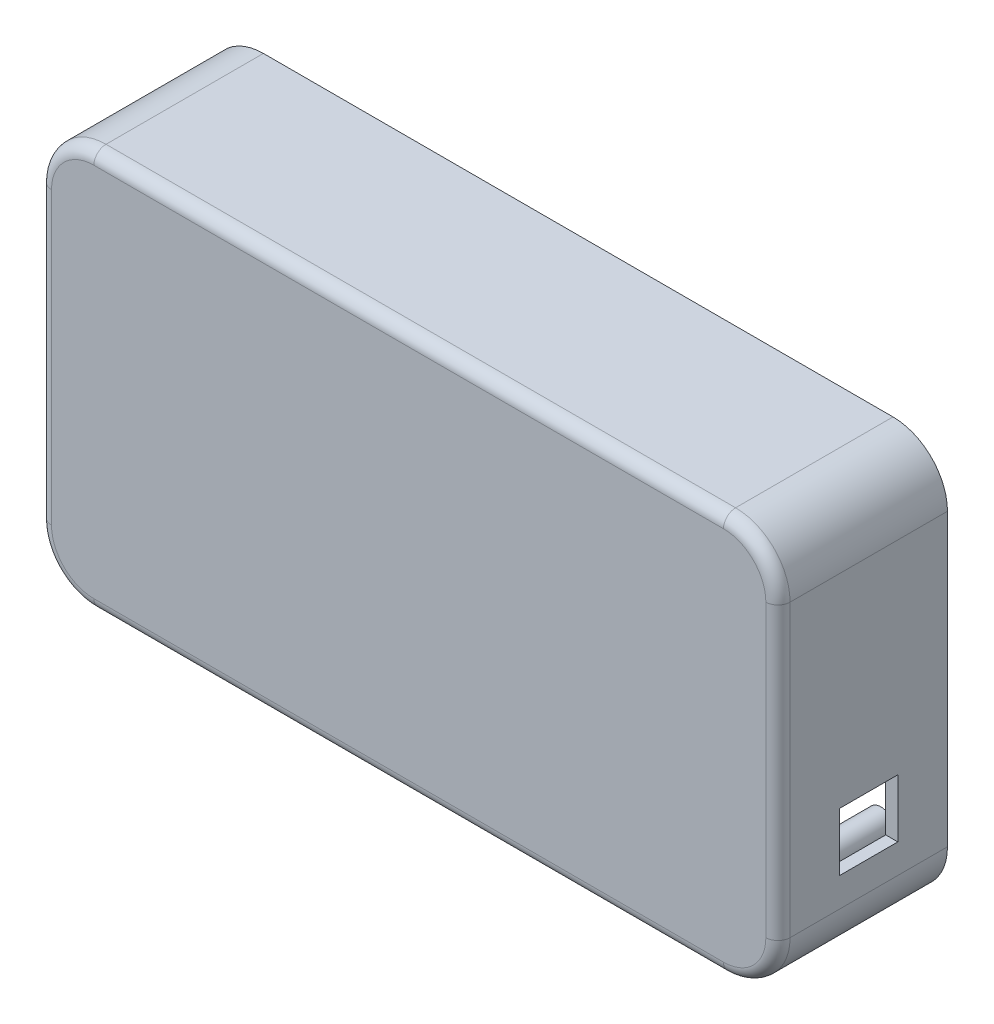
SolidWorks part; units mm, degrees
material "交联聚乙烯"
ref_plane "前视基准面" through (0, 0, 0) normal (0, 0, 1) x (1, 0, 0)
ref_plane "上视基准面" through (0, 0, 0) normal (0, 1, 0) x (1, 0, 0)
ref_plane "右视基准面" through (0, 0, 0) normal (1, 0, 0) x (0, 0, -1)
sketch "草图1" plane through (0, 0, 0) normal (0, 0, 1) x (1, 0, 0)
  line L1 (-130, 82.5) -> (130, 82.5)
  line L2 (-152.5, 60) -> (-152.5, -60)
  line L3 (-130, -82.5) -> (130, -82.5)
  line L4 (152.5, 60) -> (152.5, -60)
  line L5 (0, -82.5) -> (0, 82.5) construction
  line L6 (-152.5, 0) -> (152.5, 0) construction
  line L14 (-130, 77.5) -> (130, 77.5)
  line L15 (147.5, 60) -> (147.5, -60)
  line L16 (-130, -77.5) -> (130, -77.5)
  line L17 (-147.5, 60) -> (-147.5, -60)
  line L18 (-150.2, 60) -> (-150.2, -60)
  line L19 (-130, -80.2) -> (130, -80.2)
  line L20 (150.2, 60) -> (150.2, -60)
  line L21 (-130, 80.2) -> (130, 80.2)
  arc A0 (-130, -82.5) -> (-152.5, -60) centre (-130, -60) cw
  arc A1 (130, -82.5) -> (152.5, -60) centre (130, -60) ccw
  arc A2 (152.5, 60) -> (130, 82.5) centre (130, 60) ccw
  arc A3 (-152.5, 60) -> (-130, 82.5) centre (-130, 60) cw
  arc A12 (147.5, 60) -> (130, 77.5) centre (130, 60) ccw
  arc A13 (130, -77.5) -> (147.5, -60) centre (130, -60) ccw
  arc A14 (-130, -77.5) -> (-147.5, -60) centre (-130, -60) cw
  arc A15 (-147.5, 60) -> (-130, 77.5) centre (-130, 60) cw
  circle A16 centre (130, 60) radius 2.55
  circle A17 centre (130, 60) radius 5.55
  circle A18 centre (130, -60) radius 2.55
  circle A19 centre (130, -60) radius 5.55
  circle A20 centre (-130, 60) radius 2.55
  circle A21 centre (-130, 60) radius 5.55
  circle A22 centre (-130, -60) radius 2.55
  circle A23 centre (-130, -60) radius 5.55
  arc A24 (-130, -80.2) -> (-150.2, -60) centre (-130, -60) cw
  arc A25 (130, -80.2) -> (150.2, -60) centre (130, -60) ccw
  arc A26 (150.2, 60) -> (130, 80.2) centre (130, 60) ccw
  arc A27 (-150.2, 60) -> (-130, 80.2) centre (-130, 60) cw
  point P0 (0, 0)
  point P6 (-152.5, -82.5)
  point P9 (152.5, -82.5)
  point P12 (152.5, 82.5)
  point P49 (0, 0)
  dimension "D3" = 22.5
  dimension "D6" = 5.1
  dimension "D8" = 5.1
  dimension "D10" = 5.1
  dimension "D12" = 5.1
  dimension "D1" = 305
  dimension "D2" = 165
  dimension "D4" = 2.3
  dimension "D7" = 3
  dimension "D9" = 3
  dimension "D11" = 3
  dimension "D13" = 3
extrude "凸台-拉伸1" add sketch "草图1" along normal blind 70 contours A3 L1 A2 L4 A1 L3 A0 L2
extrude "切除-拉伸1" cut sketch "草图1<4>" along normal blind 65 contours A15 L17 A14 L16 A13 L15 A12 L14 region at (0, 0, 0)
sketch "草图1<4>" plane through (0, 0, 0) normal (0, 0, 1) x (1, 0, 0) same geometry as "草图1"
sketch "草图3" plane through (0, 0, 0) normal (0, 0, -1) x (-1, 0, 0)
extrude "切除-拉伸2" cut sketch "草图1<5>" along normal blind 5 contours A27 L21 A26 L20 A25 L19 A24 L18 L17 A15 L14 A12 L15 A13 L16 A14 region at (-144.0428, 74.0428, 0)
sketch "草图1<5>" plane through (0, 0, 0) normal (0, 0, 1) x (1, 0, 0) same geometry as "草图1"
extrude "切除-拉伸3" cut sketch "草图1<6>" along normal blind 5 contours A17 A16 region at (124.607, 60, 0)
sketch "草图1<6>" plane through (0, 0, 0) normal (0, 0, 1) x (1, 0, 0) same geometry as "草图1"
extrude "切除-拉伸4" cut sketch "草图1<7>" along normal blind 40 contours A16 region at (130, 60, 0)
sketch "草图1<7>" plane through (0, 0, 0) normal (0, 0, 1) x (1, 0, 0) same geometry as "草图1"
extrude "切除-拉伸5" cut sketch "草图1<8>" along normal blind 40 contours A18 region at (130, -60, 0)
sketch "草图1<8>" plane through (0, 0, 0) normal (0, 0, 1) x (1, 0, 0) same geometry as "草图1"
extrude "切除-拉伸6" cut sketch "草图1<10>" along normal blind 40 contours A22 region at (-130, -60, 0)
sketch "草图1<10>" plane through (0, 0, 0) normal (0, 0, 1) x (1, 0, 0) same geometry as "草图1"
extrude "切除-拉伸7" cut sketch "草图1<11>" along normal blind 40 contours A20 region at (-130, 60, 0)
sketch "草图1<11>" plane through (0, 0, 0) normal (0, 0, 1) x (1, 0, 0) same geometry as "草图1"
extrude "切除-拉伸8" cut sketch "草图1<12>" along normal blind 5 contours A21 A20 region at (-135.393, 60, 0)
sketch "草图1<12>" plane through (0, 0, 0) normal (0, 0, 1) x (1, 0, 0) same geometry as "草图1"
extrude "切除-拉伸9" cut sketch "草图1<13>" along normal blind 5 contours A23 A22 region at (-135.393, -60, 0)
sketch "草图1<13>" plane through (0, 0, 0) normal (0, 0, 1) x (1, 0, 0) same geometry as "草图1"
extrude "切除-拉伸10" cut sketch "草图1<14>" along normal blind 5 contours A19 A18 region at (124.607, -60, 0)
sketch "草图1<14>" plane through (0, 0, 0) normal (0, 0, 1) x (1, 0, 0) same geometry as "草图1"
fillet "圆角2" radius 5 4 edges at (-152.5, 0, 70) (0, -82.5, 70) (152.5, 0, 70) (0, 82.5, 70) type face fillet first side face at (0, 0, 70) second side face at (-152.5, 0, 35) second side face at (0, -82.5, 35) second side face at (152.5, 0, 35) second side face at (0, 82.5, 35)
sketch3d "3D草图1"
  point P0 (44.0813, -82.5, 36.7135)
sketch "草图14" plane through (0, -82.5, 0) normal (0, -1, 0) x (1, 0, 0)
  line L1 (25, 65) -> (-25, 65)
  line L2 (25, 65) -> (25, 45)
  line L3 (25, 45) -> (-25, 45)
  line L4 (-25, 65) -> (-25, 45)
  line L5 (130, 65) -> (-130, 65) construction
  point P6 (0, 65)
  point P7 (0, 65)
  dimension "D1" = 50
  dimension "D2" = 20
extrude "切除-拉伸11" cut sketch "草图14" against normal blind 5
sketch "草图16" plane through (152.5, 0, 0) normal (1, 0, 0) x (0, 0, -1)
  line L1 (-32.5, 60.9225) -> (-32.5, 24.0444) construction
  line L2 (-65, 60) -> (0, 60) construction
  line L3 (-44.5, -24) -> (-20.5, -24)
  line L4 (-44.5, -24) -> (-44.5, -48)
  line L5 (-44.5, -48) -> (-20.5, -48)
  line L6 (-20.5, -24) -> (-20.5, -48)
  line L7 (-32.5, -48) -> (-32.5, -24) construction
  line L8 (-44.5, -36) -> (-20.5, -36) construction
  line L9 (-65, -60) -> (0, -60) construction
  point P0 (-32.5, -36)
  point P8 (-32.5, 60)
  point P11 (-32.5, -60)
  dimension "D1" = 24
  dimension "D2" = 24
  dimension "D3" = 12
extrude "切除-拉伸12" cut sketch "草图16" against normal blind 5
sketch "草图18" plane through (-152.5, 0, 0) normal (-1, 0, 0) x (0, 0, 1)
  line L1 (32.5, 62.5) -> (32.5, 54.0347) construction
  line L2 (65, 60) -> (0, 60) construction
  line L3 (65, -60) -> (0, -60) construction
  line L4 (20.5, -24) -> (44.5, -24)
  line L5 (20.5, -24) -> (20.5, -48)
  line L6 (20.5, -48) -> (44.5, -48)
  line L7 (44.5, -24) -> (44.5, -48)
  line L8 (32.5, -48) -> (32.5, -24) construction
  line L9 (20.5, -36) -> (44.5, -36) construction
  point P2 (32.5, 60)
  point P4 (32.5, -36)
  point P11 (32.5, -60)
  dimension "D1" = 24
  dimension "D2" = 24
  dimension "D3" = 12
extrude "切除-拉伸13" cut sketch "草图18" against normal blind 5
sketch "草图19" plane through (0, 0, 65) normal (0, 0, -1) x (-1, 0, 0)
  line L0 (-103, 46) -> (-18, 46) construction
  line L1 (-103, 50) -> (-18, 50)
  line L2 (-103, 42) -> (-18, 42)
  line L3 (152.5, 0) -> (-152.5, 0) construction
  line L4 (0, -82.5) -> (0, 82.5) construction
  line L5 (-147.5, 0) -> (-107.2295, 0) construction
  line L6 (0, 77.5) -> (0, 61.8371) construction
  line L7 (103, 46) -> (18, 46) construction
  line L8 (103, 50) -> (18, 50)
  line L9 (103, 42) -> (18, 42)
  line L10 (-103, -14) -> (-18, -14) construction
  line L11 (-103, -10) -> (-18, -10)
  line L12 (-103, -18) -> (-18, -18)
  line L14 (103, -14) -> (18, -14) construction
  line L15 (103, -10) -> (18, -10)
  line L16 (103, -18) -> (18, -18)
  arc A0 (-103, 50) -> (-103, 42) centre (-103, 46) ccw
  arc A1 (-18, 42) -> (-18, 50) centre (-18, 46) ccw
  arc A2 (103, 50) -> (103, 42) centre (103, 46) cw
  arc A3 (18, 42) -> (18, 50) centre (18, 46) cw
  arc A4 (-103, -10) -> (-103, -18) centre (-103, -14) ccw
  arc A5 (-18, -18) -> (-18, -10) centre (-18, -14) ccw
  arc A6 (103, -10) -> (103, -18) centre (103, -14) cw
  arc A7 (18, -18) -> (18, -10) centre (18, -14) cw
  point P2 (-60.5, 46)
  point P13 (60.5, 46)
  point P23 (-60.5, -14)
  point P33 (60.5, -14)
  dimension "D2" = 4
  dimension "D7" = 4
  dimension "D8" = 85
  dimension "D1" = 85
  dimension "D3" = 18
  dimension "D4" = 42
  dimension "D5" = 18
  dimension "D6" = 10
extrude "凸台-拉伸2" add sketch "草图19" along normal blind 60
sketch "草图28" plane through (0, 0, 5) normal (0, 0, -1) x (-1, 0, 0)
  line L0 (103, -12) -> (18, -12) construction
  line L1 (103, -10) -> (18, -10) construction
  line L2 (18, -12) -> (18, -10) construction
  line L3 (103, -12) -> (103, -10) construction
  arc A0 (18, -10) -> (18, -18) centre (18, -14) ccw construction
  text T0 "<b>P P G E K I @ v 1 . 0  β</b>" font "微软雅黑" height 3
  dimension "D1" = 2
extrude "切除-拉伸17" cut sketch "草图28" against normal blind 1
